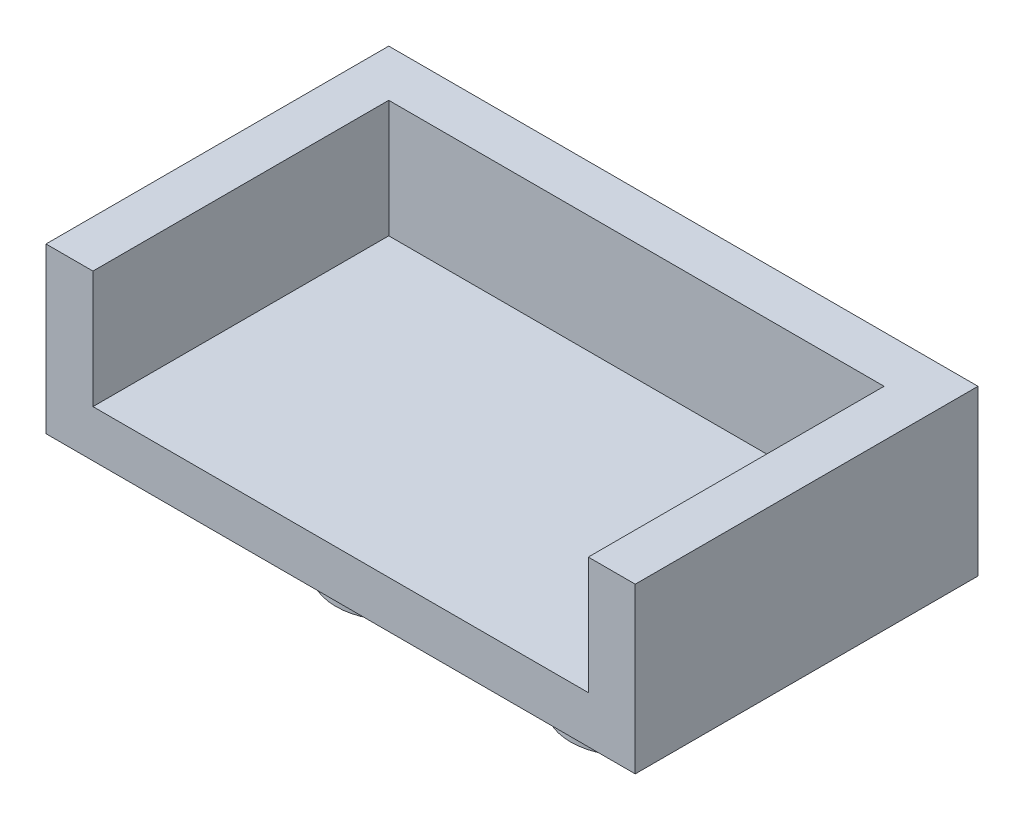
SolidWorks part; units mm, degrees
ref_plane "Front Plane" through (0, 0, 0) normal (0, 0, 1) x (1, 0, 0)
ref_plane "Top Plane" through (0, 0, 0) normal (0, 1, 0) x (1, 0, 0)
ref_plane "Right Plane" through (0, 0, 0) normal (1, 0, 0) x (0, 0, -1)
sketch "Sketch1" plane through (0, 0, 0) normal (0, 1, 0) x (1, 0, 0)
  line L0 (-2, 14.6) -> (23.1, 14.6)
  line L1 (0, 0) -> (21.1, 0)
  line L2 (0, 0) -> (0, 12.6)
  line L3 (0, 12.6) -> (21.1, 12.6)
  line L4 (21.1, 0) -> (21.1, 12.6)
  line L5 (23.1, -2) -> (23.1, 14.6)
  line L6 (-2, -2) -> (23.1, -2)
  line L7 (-2, -2) -> (-2, 14.6)
  line L8 (-2, 0) -> (0, 0)
  line L9 (21.1, 0) -> (23.1, 0)
  dimension "D1" = 12.6
  dimension "D2" = 21.1
  dimension "D3" = 2
extrude "Boss-Extrude1" add sketch "Sketch1" along normal blind 5 contours L4 L9 L5 L0 L7 L8 L2 L3 region at (10.55, 0, -14.3096)
extrude "Boss-Extrude2" add sketch "Sketch1<3>" against normal blind 2 contours L1 L4 L3 L2 | L4 L9 L5 L0 L7 L8 L2 L3 region at (10.55, 0, -14.3096) region at (10.55, 0, -6.3)
sketch "Sketch1<3>" plane through (0, 0, 0) normal (0, 1, 0) x (1, 0, 0) same geometry as "Sketch1"
sketch "Sketch2" plane through (0, 0, 0) normal (0, 1, 0) x (1, 0, 0)
  line L0 (0, 0) -> (0, 12.6) construction
  line L1 (0, 12.6) -> (21.1, 12.6) construction
  line L2 (21.1, 0) -> (21.1, 12.6) construction
  line L4 (2.6, 11.7) -> (2.6, 8.7) construction
  line L5 (2.6, 8.7) -> (18.5, 8.7) construction
  line L6 (18.5, 8.7) -> (18.5, 11.7) construction
  line L7 (2.1, 11.7) -> (2.1, 8.7)
  line L8 (19, 8.7) -> (19, 11.7)
  line L9 (3.1, 11.7) -> (3.1, 8.7)
  line L10 (18, 8.7) -> (18, 11.7)
  circle A0 centre (2.6, 10.2) radius 1.5
  circle A1 centre (18.5, 10.2) radius 1.5
  dimension "D1" = 3
  dimension "D2" = 2.6
  dimension "D3" = 2.4
  dimension "D4" = 2.6
  dimension "D5" = 0.5
  dimension "D6" = 0.5
extrude "Boss-Extrude3" [suppressed] add sketch "Sketch2" along normal blind 2 contours L9 A0 | L7 A0 | L8 A1 | L10 A1
sketch "Sketch3" plane through (0, -2, 0) normal (0, -1, 0) x (1, 0, 0)
  line L0 (10.55, 0) -> (10.55, -14.6) construction
  line L1 (-2, 0) -> (23.1, 0) construction
  line L2 (-2, -14.6) -> (23.1, -14.6) construction
  line L3 (5.55, -7.3) -> (10.55, -7.3) construction
  circle A0 centre (5.55, -7.3) radius 2.5
  circle A1 centre (15.55, -7.3) radius 2.5
  dimension "D1" = 5
  dimension "D2" = 5
extrude "Boss-Extrude4" add sketch "Sketch3" along normal blind 5
